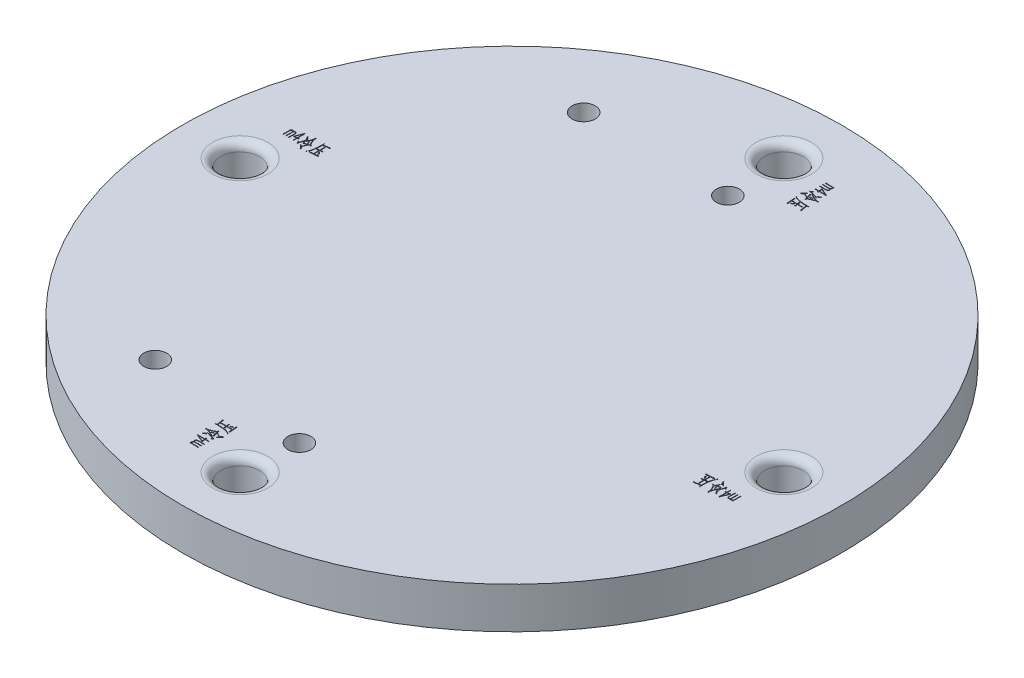
SolidWorks part; units mm, degrees
ref_plane "前视基准面" through (0, 0, 0) normal (0, 0, 1) x (1, 0, 0)
ref_plane "上视基准面" through (0, 0, 0) normal (0, 1, 0) x (1, 0, 0)
ref_plane "右视基准面" through (0, 0, 0) normal (1, 0, 0) x (0, 0, -1)
sketch "草图1" plane through (0, 0, 0) normal (0, 1, 0) x (1, 0, 0)
  line L14 (0, 0) -> (35, 0)
  line L15 (0, 0) -> (0, -35)
  circle A0 centre (0, 0) radius 40
  circle A5 centre (0, 0) radius 35
  circle A6 centre (0, 0) radius 34
  circle A7 centre (0, -34) radius 1
  circle A8 centre (0, -33) radius 2
  dimension "D1" = 80
  dimension "D2" = 70
  dimension "D3" = 68
sketch "草图3" plane through (0, 0, 0) normal (0, 1, 0) x (1, 0, 0)
  circle A0 centre (0, -33) radius 2 construction
  circle A1 centre (0, -33) radius 2
  circle A2 centre (0, 0) radius 33
  circle A3 centre (-32.999, 0.001) radius 2
  circle A4 centre (0.002, 33) radius 2
  circle A5 centre (33.001, -0.001) radius 2
  point P15 (0.001, 0)
  dimension "D2" = 4
  dimension "D1" = 4
sketch "草图4" plane through (0, 0, 0) normal (0, 1, 0) x (1, 0, 0)
  circle A0 centre (0, 0) radius 40 construction
  circle A1 centre (0, 0) radius 40
extrude "凸台-拉伸1" add sketch "草图4" along normal blind 5
sketch "草图6" plane through (0, 0, 0) normal (0, 1, 0) x (1, 0, 0)
  circle A14 centre (0.002, 33) radius 2 construction
  circle A16 centre (-32.999, 0.001) radius 2.35
  circle A17 centre (0, -33) radius 2.35
  circle A18 centre (33.001, -0.001) radius 2.35
  circle A19 centre (0.002, 33) radius 2.35
  dimension "D2" = 4.7
extrude "固定轴承内圈的四个冷压孔" cut sketch "草图6" along normal up to surface (5 mm away) up to face at (0, 5, 40)
fillet "圆角1" radius 1 4 edges at (0.002, 5, -30.65) (33.001, 5, 2.351) (0, 5, 35.35) (-32.999, 5, 2.349)
ref_plane "基准面1" through (0, 5, 0) normal (0, 1, 0) x (1, 0, 0)
sketch "草图8" plane through (0, 5, 0) normal (0, 1, 0) x (1, 0, 0)
  line L0 (0.002, 33) -> (-32.999, 0.001)
  line L1 (0.002, 33) -> (33.001, -0.001)
  line L2 (-32.999, 0.001) -> (0, -33)
  line L3 (33.001, -0.001) -> (0, -33)
  line L5 (33.001, -0.001) -> (28.0007, -0.001)
  line L6 (33.001, -0.001) -> (33.001, -5.001)
  line L7 (33.001, -5.001) -> (28.0007, -5.001)
  line L8 (28.0007, -0.001) -> (28.0007, -5.001)
  line L9 (0.002, 33) -> (5.002, 33)
  line L10 (0.002, 33) -> (0.002, 27.9997)
  line L11 (0.002, 27.9997) -> (5.002, 27.9997)
  line L12 (5.002, 33) -> (5.002, 27.9997)
  line L13 (-32.999, 0.001) -> (-27.9987, 0.001)
  line L14 (-32.999, 0.001) -> (-32.999, 5.001)
  line L15 (-32.999, 5.001) -> (-27.9987, 5.001)
  line L16 (-27.9987, 0.001) -> (-27.9987, 5.001)
  line L17 (0, -33) -> (-5, -33)
  line L18 (0, -33) -> (0, -27.9997)
  line L19 (0, -27.9997) -> (-5, -27.9997)
  line L20 (-5, -33) -> (-5, -27.9997)
  circle A0 centre (0, 0) radius 33
  circle A1 centre (-32.999, 0.001) radius 2.35 construction
  circle A2 centre (-32.999, 0.001) radius 2.35
  circle A3 centre (0.002, 33) radius 2.35 construction
  circle A4 centre (0.002, 33) radius 2.35
  circle A5 centre (0, -33) radius 2.35 construction
  circle A6 centre (0, -33) radius 2.35
  circle A7 centre (0, 0) radius 40 construction
  circle A8 centre (0, 0) radius 40
  dimension "D1" = 5
  dimension "D5" = 66
  dimension "D6" = 80
  dimension "D2" = 5
  dimension "D3" = 5
  dimension "D4" = 5
sketch "草图9" plane through (0, 5, 0) normal (0, 1, 0) x (1, 0, 0)
  text T0 "m4冷压" font "汉仪长仿宋体" height 1.5
  text T1 "m4冷压" font "汉仪长仿宋体" height 1.5
  text T2 "m4冷压" font "汉仪长仿宋体" height 1.5
  text T3 "m4冷压\r\n" font "汉仪长仿宋体" height 1.5
extrude "切除-拉伸1" cut sketch "草图9" against normal blind 0.5
sketch "草图10" plane through (0, 5, 0) normal (0, 1, 0) x (1, 0, 0)
  line L0 (-15.7182, 20.6662) -> (-25.7182, 20.6662)
  line L1 (-25.7182, 20.6662) -> (-25.7182, -21.3338)
  line L2 (-25.7182, -21.3338) -> (-15.7182, -21.3338)
  line L3 (-15.7182, -21.3338) -> (-15.7182, 20.6662)
  line L4 (4.7818, 30.6662) -> (4.7818, -31.3338)
  line L5 (25.2818, -21.3338) -> (25.2818, 20.6662)
  line L6 (22.2818, 30.6662) -> (4.7818, 20.6662)
  line L7 (22.2818, 30.6662) -> (22.2818, -31.3338)
  line L8 (-12.7182, 30.6662) -> (-15.7182, 30.6662)
  line L9 (-15.7182, 30.6662) -> (-15.7182, -31.3338)
  line L10 (-15.7182, -31.3338) -> (-12.7182, -31.3338)
  line L11 (-12.7182, -31.3338) -> (-12.7182, 30.6662)
  line L12 (22.2818, 20.6662) -> (22.2818, 30.6662)
  line L13 (22.2818, 30.6662) -> (-12.7182, 30.6662)
  line L14 (-12.7182, 30.6662) -> (-12.7182, 20.6662)
  line L15 (-12.7182, 20.6662) -> (22.2818, 20.6662)
  line L16 (22.2818, -31.3338) -> (22.2818, -21.3338)
  line L17 (-12.7182, -31.3338) -> (22.2818, -31.3338)
  line L18 (-12.7182, -21.3338) -> (-12.7182, -31.3338)
  line L19 (22.2818, -21.3338) -> (-12.7182, -21.3338)
  line L20 (22.2818, 20.6662) -> (-12.7182, 20.6662)
  line L21 (-12.7182, 20.6662) -> (-12.7182, -21.3338)
  line L22 (-12.7182, -21.3338) -> (22.2818, -21.3338)
  line L23 (22.2818, -21.3338) -> (22.2818, 20.6662)
  line L24 (22.2818, -21.3338) -> (25.2818, -21.3338)
  line L25 (22.2818, 20.6662) -> (25.2818, 20.6662)
  line L26 (-12.7182, -21.3338) -> (-15.7182, -21.3338)
  line L27 (-12.7182, 20.6662) -> (-15.7182, 20.6662)
  line L28 (22.2818, 20.6662) -> (4.7818, 30.6662)
  line L29 (4.7818, 30.6662) -> (-12.7182, 20.6662)
  line L30 (4.7818, 20.6662) -> (-12.7182, 30.6662)
  line L31 (22.2818, -21.3338) -> (4.7818, -31.3338)
  line L32 (22.2818, -31.3338) -> (4.7818, -21.3338)
  line L33 (4.7818, -21.3338) -> (-12.7182, -31.3338)
  line L34 (4.7818, -31.3338) -> (-12.7182, -21.3338)
  circle A0 centre (0, 0) radius 33
  circle A1 centre (13.5318, 25.6662) radius 1.4
  circle A2 centre (-3.9682, 25.6662) radius 1.4
  circle A3 centre (13.5318, -26.3338) radius 1.4
  circle A4 centre (-3.9682, -26.3338) radius 1.4
  dimension "D1" = 66
  dimension "D2" = 2.8
  dimension "D3" = 2.8
  dimension "D4" = 2.8
  dimension "D5" = 2.8
sketch "草图11" plane through (0, 5, 0) normal (0, 1, 0) x (1, 0, 0)
  circle A0 centre (0.5318, -26.3338) radius 1.4
  circle A1 centre (0.5318, 25.6662) radius 1.4
  circle A2 centre (-16.9682, 25.6662) radius 1.4
  circle A3 centre (-16.9682, -26.3338) radius 1.4
extrude "切除-拉伸2" cut sketch "草图11" against normal up to surface (5 mm away) up to face at (-32.999, 0, 2.349)
